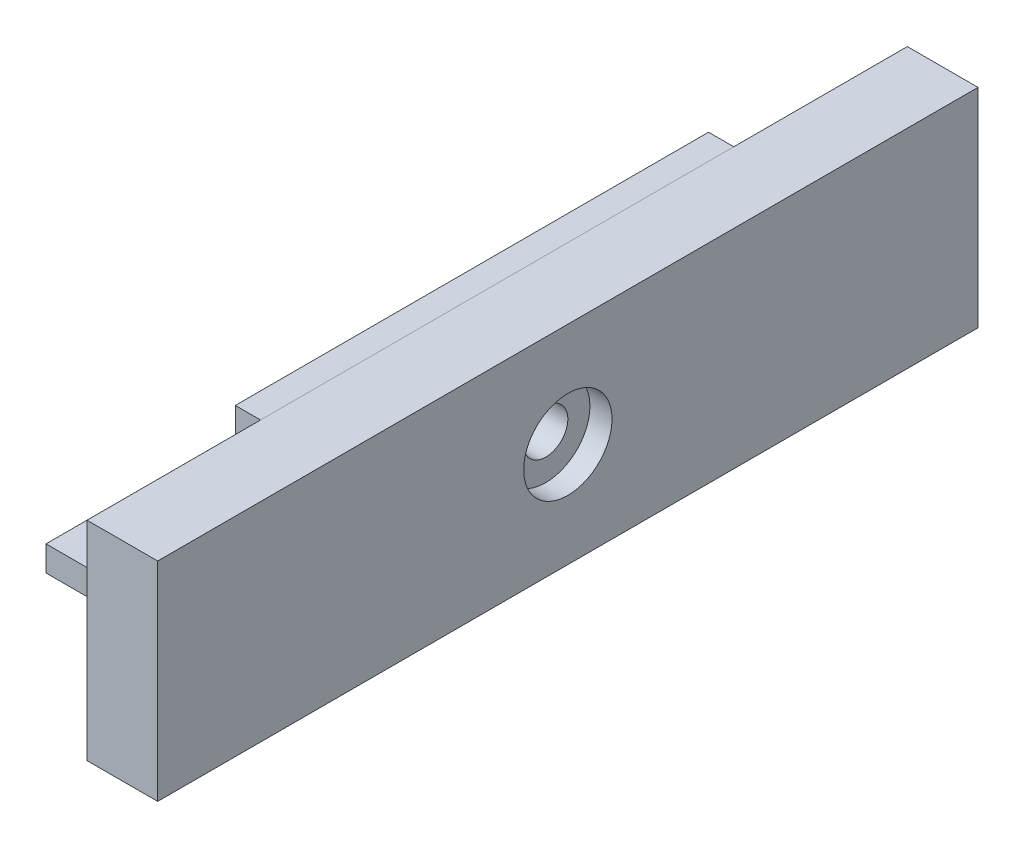
SolidWorks part; units mm, degrees
material "AISI 1020 Steel, Cold Rolled"
ref_plane "Front Plane" through (0, 0, 0) normal (0, 0, 1) x (1, 0, 0)
ref_plane "Top Plane" through (0, 0, 0) normal (0, 1, 0) x (1, 0, 0)
ref_plane "Right Plane" through (0, 0, 0) normal (1, 0, 0) x (0, 0, -1)
sketch "Sketch1" plane through (0, 0, 0) normal (1, 0, 0) x (0, 0, -1)
  line L1 (-65, 16.5) -> (65, 16.5)
  line L2 (-65, 16.5) -> (-65, -16.5)
  line L3 (-65, -16.5) -> (65, -16.5)
  line L4 (65, 16.5) -> (65, -16.5)
  line L5 (0, -16.5) -> (0, 16.5) construction
  line L6 (-65, 0) -> (65, 0) construction
  circle A0 centre (0, 0) radius 3.5
  point P0 (0, 0)
  dimension "D3" = 7
  dimension "D1" = 130
  dimension "D2" = 33
extrude "Boss-Extrude1" add sketch "Sketch1" along normal blind 11.2
sketch "Sketch2" plane through (11.2, 0, 0) normal (1, 0, 0) x (0, 0, -1)
  circle A0 centre (0, 0) radius 7
  dimension "D1" = 14
extrude "Cut-Extrude1" cut sketch "Sketch2" against normal blind 3.5
sketch "Sketch3" plane through (0, 0, 0) normal (-1, 0, 0) x (0, 0, 1)
  line L0 (-65, 16.5) -> (65, 16.5) construction
  line L1 (0, -16.5) -> (-37.5, -16.5) construction
  line L2 (37.5, -16.5) -> (37.5, 16.5)
  line L3 (37.5, 16.5) -> (-37.5, 16.5)
  line L4 (-37.5, -16.5) -> (-37.5, 16.5)
  line L5 (0, 16.5) -> (0, -16.5) construction
  line L6 (37.5, 0) -> (-37.5, 0) construction
  line L8 (37.5, 16.5) -> (-37.5, 16.5)
  line L12 (0, -16.5) -> (-37.5, -16.5) construction
  line L13 (37.5, -16.5) -> (37.5, -21.5)
  line L14 (37.5, -21.5) -> (-37.5, -21.5)
  line L15 (-37.5, -16.5) -> (-37.5, -21.5)
  line L16 (37.5, -21.5) -> (-37.5, -21.5)
  line L17 (37.5, -21.5) -> (37.5, 16.5)
  line L18 (37.5, 16.5) -> (-37.5, 16.5)
  line L19 (-37.5, -21.5) -> (-37.5, 16.5)
  circle A0 centre (0, 0) radius 3.5
  point P0 (0, 0)
  line M6 (-65, -16.5) -> (65, -16.5)
  line M8 (65, 16.5) -> (-65, 16.5)
  circle M9 centre (0, 0) radius 3.5
  dimension "D1" = 75
  dimension "D2" = 5
extrude "Boss-Extrude2" add sketch "Sketch3" along normal blind 4 contours L4 L2 M6 M8 M9 | M8 region at (0, -15.6806, 0)
extrude "Boss-Extrude4" add sketch "Sketch3<3>" along normal blind 4 separate body contours L4 L2 M6 M8 M9 | L15 L14 L13 M6 region at (0, -15.6806, 0) region at (0, -19, 0)
sketch "Sketch3<3>" plane through (0, 0, 0) normal (-1, 0, 0) x (0, 0, 1) same geometry as "Sketch3"
sketch "Sketch6" plane through (-4, 0, 0) normal (-1, 0, 0) x (0, 0, 1)
  line L0 (-37.5, 16.5) -> (-37.5, -21.5) construction
  line L1 (37.5, -21.5) -> (-37.5, -21.5)
  line L2 (37.5, -21.5) -> (37.5, -17.498)
  line L3 (37.5, -17.498) -> (-37.5, -17.498)
  line L4 (-37.5, -21.5) -> (-37.5, -17.498)
  dimension "D1" = 4.002
extrude "Boss-Extrude6" add sketch "Sketch6" along normal blind 30
